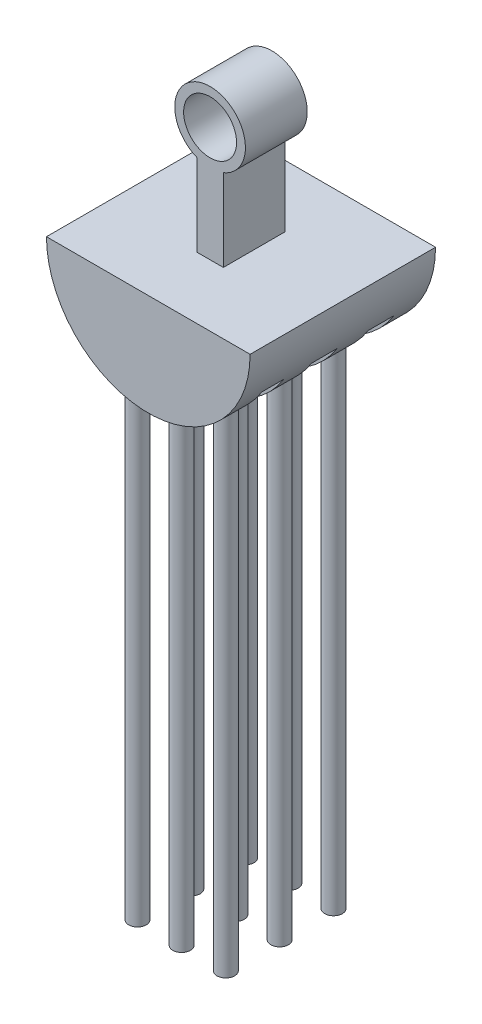
SolidWorks part; units mm, degrees
ref_plane "Front Plane" through (0, 0, 0) normal (0, 0, 1) x (1, 0, 0)
ref_plane "Top Plane" through (0, 0, 0) normal (0, 1, 0) x (1, 0, 0)
ref_plane "Right Plane" through (0, 0, 0) normal (1, 0, 0) x (0, 0, -1)
sketch "Sketch2" plane through (0, 0, 0) normal (0, 0, 1) x (1, 0, 0)
  circle A0 centre (0, 0) radius 3
  circle A1 centre (0, 0) radius 4
extrude "Boss-Extrude1" add sketch "Sketch2" along normal blind 7
sketch "Sketch3" plane through (0, 0, 7) normal (0, 0, 1) x (1, 0, 0)
  line L0 (0, -3) -> (-1.5, -3)
  line L1 (-1.5, -3) -> (-1.5, -13)
  line L2 (-1.5, -13) -> (1.5, -13)
  line L3 (1.5, -13) -> (1.5, -3)
  line L4 (1.5, -3) -> (0, -3)
  circle A0 centre (0, 0) radius 3 construction
extrude "Boss-Extrude2" add sketch "Sketch3" against normal blind 7
sketch "Sketch4" plane through (0, 0, 7) normal (0, 0, 1) x (1, 0, 0)
  line L0 (1.5, -13) -> (11.5313, -13)
  line L1 (1.5, -13) -> (-1.5, -13)
  line L2 (-1.5, -13) -> (-11.5313, -13)
  arc A0 (-11.5313, -13) -> (11.5313, -13) centre (0, -13) ccw
extrude "Boss-Extrude3" add sketch "Sketch4" along normal blind 7 and the other way blind 14
sketch "Sketch5" plane through (1.5, 0, 0) normal (1, 0, 0) x (0, 0, -1)
  line L1 (-10.9017, -19.1088) -> (-8.4203, -19.1088)
  line L2 (-10.9017, -19.1088) -> (-10.9017, -30.358)
  line L3 (-10.9017, -30.358) -> (-8.4203, -30.358)
  line L4 (-8.4203, -19.1088) -> (-8.4203, -30.358)
  line L5 (-8.4203, -30.358) -> (0.568, -30.358)
  line L6 (-8.4203, -30.358) -> (-8.4203, -32.3431)
  line L7 (-8.4203, -32.3431) -> (0.568, -32.3431)
  line L8 (0.568, -30.358) -> (0.568, -32.3431)
  line L9 (-5.2772, -19.1088) -> (-2.4097, -19.1088)
  line L10 (-5.2772, -19.1088) -> (-5.2772, -30.358)
  line L11 (-5.2772, -30.358) -> (-2.4097, -30.358)
  line L12 (-2.4097, -19.1088) -> (-2.4097, -30.358)
  line L13 (1.1194, -19.1088) -> (4.042, -19.1088)
  line L14 (1.1194, -19.1088) -> (1.1194, -30.358)
  line L15 (1.1194, -30.358) -> (4.042, -30.358)
  line L16 (4.042, -19.1088) -> (4.042, -30.358)
  point P15 (0, 0)
  point P16 (1.1194, -19.1088)
  point P17 (4.042, -19.1088)
extrude "Cut-Extrude2" cut sketch "Sketch5" against normal blind 169 and the other way blind 169 contours L4 L1 L2 L3 | L12 L9 L10 L5 | L16 L13 L14 L15 region at (1.5, -24.7334, 9.661) region at (1.5, -24.7334, 3.8434) region at (1.5, -24.7334, -2.5807)
sketch "Sketch6" plane through (0, -19.1088, 0) normal (0, -1, 0) x (1, 0, 0)
  circle A0 centre (-5.4862, 9.7343) radius 1
  circle A1 centre (-0.4862, 9.7343) radius 1
  circle A2 centre (4.5138, 9.7343) radius 1
  circle A3 centre (-0.4862, 3.6343) radius 1
  circle A4 centre (4.5138, 3.6343) radius 1
  circle A5 centre (-0.4862, -2.4657) radius 1
  circle A6 centre (4.5138, -2.4657) radius 1
  circle A7 centre (-5.4862, 3.6343) radius 1
  circle A8 centre (-5.4862, -2.4657) radius 1
  dimension "D1" = 3
  dimension "D2" = 3
extrude "Boss-Extrude5" add sketch "Sketch6" along normal blind 60
